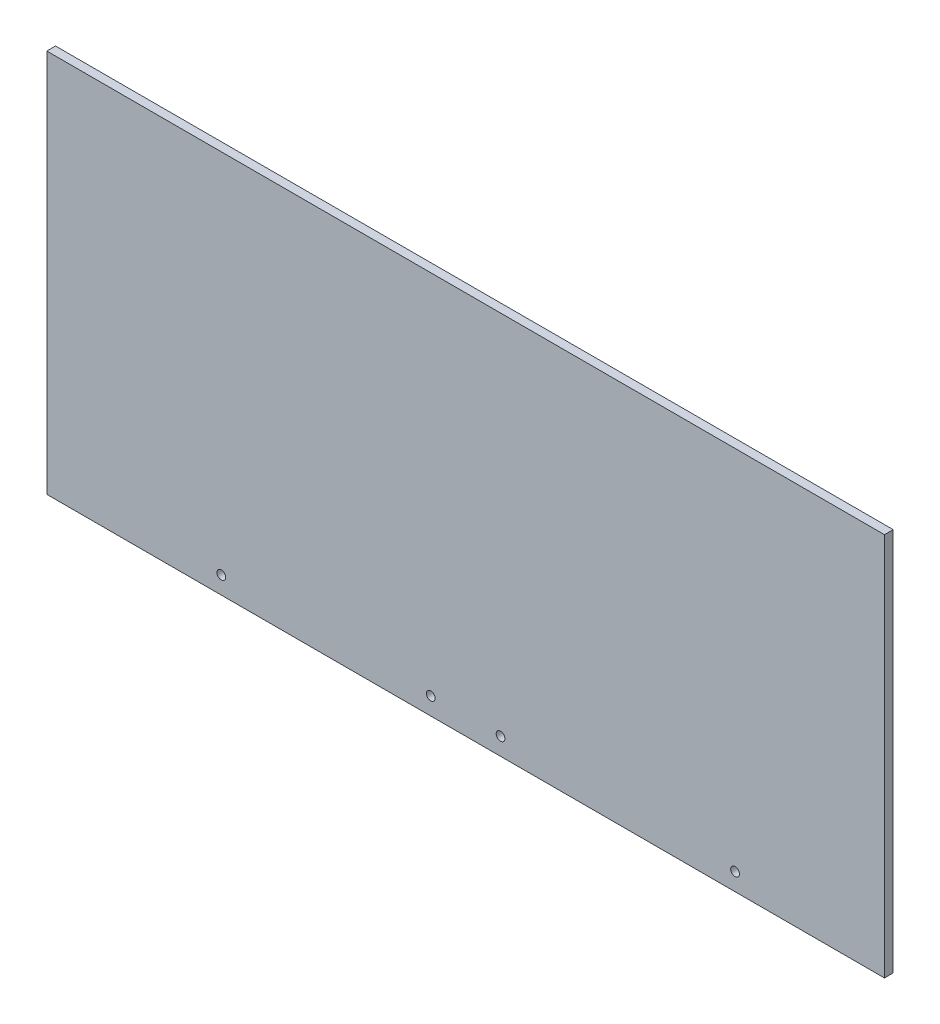
SolidWorks part; units mm, degrees
ref_plane "Front Plane" through (0, 0, 0) normal (0, 0, 1) x (1, 0, 0)
ref_plane "Top Plane" through (0, 0, 0) normal (0, 1, 0) x (1, 0, 0)
ref_plane "Right Plane" through (0, 0, 0) normal (1, 0, 0) x (0, 0, -1)
sketch "Sketch1" plane through (0, 0, 0) normal (0, 0, 1) x (1, 0, 0)
  line L0 (-324.8121, -188.8323) -> (284.7879, -188.8323) construction
  line L1 (-172.4121, 77.8677) -> (-20.0121, 77.8677)
  line L2 (-172.4121, 77.8677) -> (-172.4121, -201.5323)
  line L3 (-172.4121, -201.5323) -> (-20.0121, -201.5323)
  line L4 (-20.0121, 77.8677) -> (-20.0121, -201.5323)
  line L5 (-172.4121, 77.8677) -> (-20.0121, -201.5323) construction
  line L6 (-172.4121, -201.5323) -> (-20.0121, 77.8677) construction
  line L7 (-20.0121, 77.8677) -> (132.3879, 77.8677)
  line L8 (-20.0121, 77.8677) -> (-20.0121, -201.5323)
  line L9 (-20.0121, -201.5323) -> (132.3879, -201.5323)
  line L10 (132.3879, 77.8677) -> (132.3879, -201.5323)
  line L11 (-20.0121, 77.8677) -> (132.3879, -201.5323) construction
  line L12 (-20.0121, -201.5323) -> (132.3879, 77.8677) construction
  line L13 (132.3879, 77.8677) -> (284.7879, 77.8677)
  line L14 (132.3879, 77.8677) -> (132.3879, -201.5323)
  line L15 (132.3879, -201.5323) -> (284.7879, -201.5323)
  line L16 (284.7879, 77.8677) -> (284.7879, -201.5323)
  line L17 (132.3879, 77.8677) -> (284.7879, -201.5323) construction
  line L18 (132.3879, -201.5323) -> (284.7879, 77.8677) construction
  line L19 (-172.4121, 77.8677) -> (-324.8121, 77.8677)
  line L20 (-172.4121, 77.8677) -> (-172.4121, -201.5323)
  line L21 (-172.4121, -201.5323) -> (-324.8121, -201.5323)
  line L22 (-324.8121, 77.8677) -> (-324.8121, -201.5323)
  line L23 (-172.4121, 77.8677) -> (-324.8121, -201.5323) construction
  line L24 (-172.4121, -201.5323) -> (-324.8121, 77.8677) construction
  circle A0 centre (-197.8121, -188.8323) radius 3.175
  circle A1 centre (-45.4121, -188.8323) radius 3.175
  circle A2 centre (5.3879, -188.8323) radius 3.175
  circle A3 centre (176.0505, -188.8323) radius 3.175
  point P4 (-96.2121, -61.8323)
  point P7 (56.1879, -61.8323)
  point P10 (208.5879, -61.8323)
  point P14 (-248.6121, -61.8323)
  point P25 (-195.503, -188.8323)
  dimension "D8" = 6.35
  dimension "D1" = 152.4
  dimension "D2" = 12.7
  dimension "D3" = 152.4
  dimension "D4" = 50.8
  dimension "D5" = 170.6626
  dimension "D6" = 25.4
  dimension "D7" = 279.4
extrude "Boss-Extrude1" add sketch "Sketch1" along normal blind 6.35 contours L19 L22 L21 L2 A0 | L4 L1 L2 L3 A1 | L10 L7 L4 L9 A2 | L16 L13 L10 L15 A3 region at (-96.2499, -61.7378, 0) region at (-248.6499, -61.7378, 0) region at (56.2257, -61.7378, 0) region at (208.6121, -61.7378, 0)
